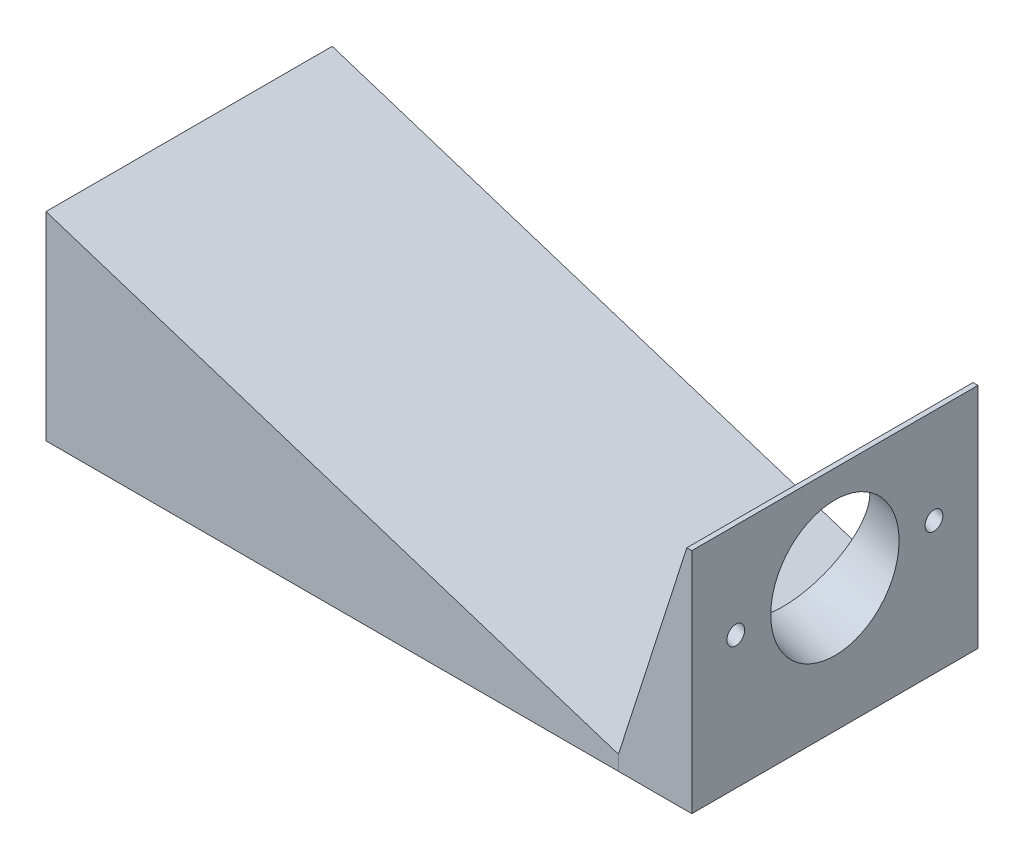
SolidWorks part; units mm, degrees
ref_plane "Alzado" through (0, 0, 0) normal (0, 0, 1) x (1, 0, 0)
ref_plane "Planta" through (0, 0, 0) normal (0, 1, 0) x (1, 0, 0)
ref_plane "Vista lateral" through (0, 0, 0) normal (1, 0, 0) x (0, 0, -1)
sketch "Croquis1" plane through (0, 0, 0) normal (0, 0, 1) x (1, 0, 0)
  line L0 (-29, 0) -> (29, 0)
  line L1 (-29, 0) -> (-29, 20.1218)
  line L3 (-29, 20.1218) -> (29, 1.5)
  line L4 (29, 1.5) -> (28.8666, 1.5) construction
  line L6 (29, 1.5) -> (-29, 1.5) construction
  line L11 (29, 1.5) -> (29, 0)
  point P4 (0, 0)
  dimension "D1" = 58
  dimension "D2" = 17.8
  dimension "D3" = 1.5
extrude "Saliente-Extruir1" add sketch "Croquis1" against normal blind 29
sketch "Croquis3" plane through (0, 0, 0) normal (0, 0, 1) x (1, 0, 0)
  line L0 (29, 0) -> (29, 1.5)
  line L1 (29, 1.5) -> (35.9299, 23.0841)
  line L2 (35.9299, 23.0841) -> (36.4299, 23.0841)
  line L3 (36.4299, 23.0841) -> (36.4299, 0)
  line L4 (36.4299, 0) -> (29, 0)
  line L5 (29, 1.5) -> (-29, 1.5) construction
  line L6 (-29, 20.1218) -> (-29, 0) construction
  line L7 (29, 1.5) -> (36.4299, 1.5) construction
  line L8 (29, 1.5) -> (-29, 20.1218) construction
  dimension "D1" = 0.5
  dimension "D2" = 90
extrude "Saliente-Extruir2" add sketch "Croquis3" against normal blind 29 separate body
sketch "Croquis6" plane through (25.8534, -8.3006, 0) normal (-0.9521, 0.3057, 0) x (0, 0, 1)
  line L0 (-14.5, 10.2934) -> (-14.5, 32.9627) construction
  line L1 (-29, 10.2934) -> (0, 10.2934) construction
  line L2 (-29, 32.9627) -> (0, 32.9627) construction
  circle A0 centre (-14.5, 23.9434) radius 6.5
  dimension "D1" = 13
  dimension "D2" = 13.65
extrude "Cortar-Extruir1" cut sketch "Croquis6" against normal through all
sketch "Croquis9" plane through (25.8534, -8.3006, 0) normal (-0.9521, 0.3057, 0) x (0, 0, 1)
  line L0 (-14.5, 23.9434) -> (-24.54, 23.9434) construction
  line L3 (-14.5, 23.9434) -> (-14.5, 10.2934) construction
  line L4 (-29, 10.2934) -> (0, 10.2934) construction
  circle A0 centre (-14.5, 23.9434) radius 6.5 construction
  circle A1 centre (-14.5, 23.9434) radius 6.5
  circle A2 centre (-24.54, 23.9434) radius 0.9
  circle A3 centre (-4.46, 23.9434) radius 0.9
  dimension "D2" = 1.8
  dimension "D1" = 10.04
extrude "Cortar-Extruir2" cut sketch "Croquis9" against normal through all
sketch "Croquis10" plane through (0, 0, 0) normal (0, -1, 0) x (1, 0, 0)
  line L0 (32.715, 0) -> (32.715, -29) construction
  line L1 (29, 0) -> (36.4299, 0) construction
  line L2 (29, -29) -> (36.4299, -29) construction
  line L3 (-23.285, 0) -> (-23.285, -29) construction
  line L4 (-29, 0) -> (29, 0) construction
  line L5 (-29, -29) -> (29, -29) construction
  line L6 (4.715, 0) -> (4.715, -29) construction
  circle A0 centre (-23.285, -6) radius 1.5
  circle A1 centre (-23.285, -23) radius 1.5
  circle A2 centre (32.715, -6) radius 1.5
  circle A3 centre (32.715, -23) radius 1.5
  circle A4 centre (4.715, -14.5) radius 1.5
  point P24 (0, 0)
  point P25 (0, 0)
  point P26 (0, 0)
  dimension "D3" = 3
  dimension "D1" = 28
  dimension "D2" = 28
  dimension "D4" = 6
  dimension "D5" = 6
extrude "Cortar-Extruir3" cut sketch "Croquis10" against normal blind 4
